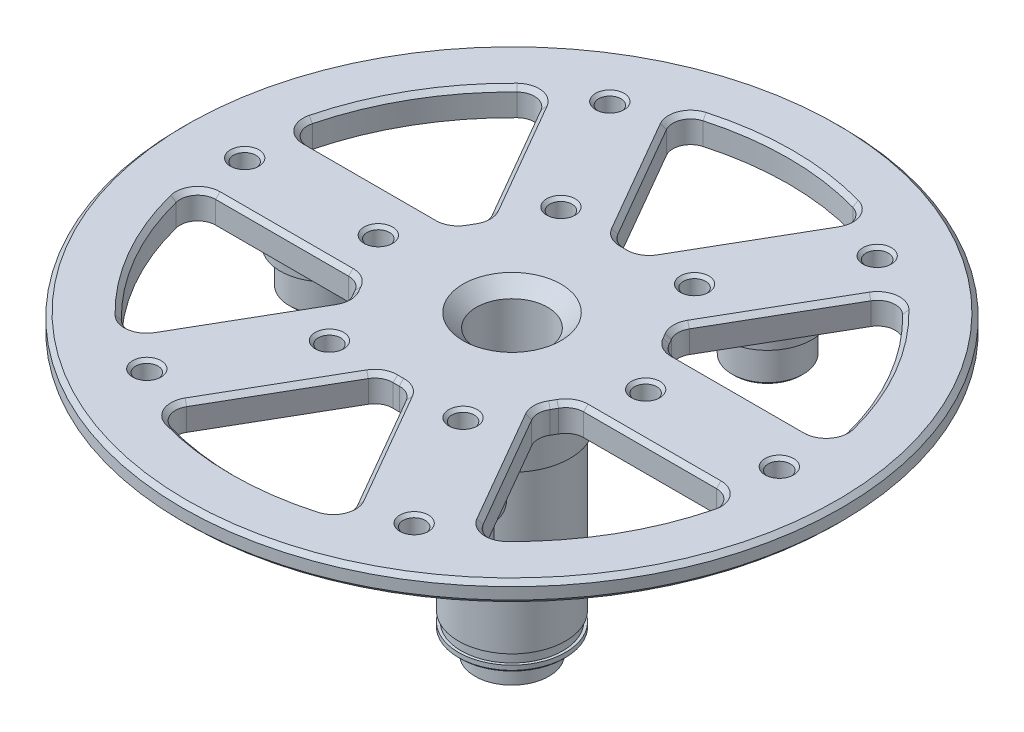
SolidWorks part; units mm, degrees
ref_plane "Front Plane" through (0, 0, 0) normal (0, 0, 1) x (1, 0, 0)
ref_plane "Top Plane" through (0, 0, 0) normal (0, 1, 0) x (1, 0, 0)
ref_plane "Right Plane" through (0, 0, 0) normal (1, 0, 0) x (0, 0, -1)
ref_axis "Axis1" through (0, 0, 0) along (0, 1, 0)
sketch "Sketch1" plane through (0, 0, 0) normal (0, 0, 1) x (1, 0, 0)
  line L0 (0, 0) -> (0, -6072.8457) construction
  line L2 (-3.15, -8.7) -> (-4, -8.7)
  line L3 (-4, -8.7) -> (-4, 19.6)
  line L4 (-4, 19.6) -> (-5.5, 21.1)
  line L5 (-5.5, 21.1) -> (-37, 21.1)
  line L6 (-32, 18.8) -> (-32, 18.1)
  line L7 (-32, 18.1) -> (-6.5, 18.1)
  line L8 (-6.5, 18.1) -> (-6.5, 10.15)
  line L9 (-6.5, 10.15) -> (-6, 10.15)
  line L10 (-6, 10.15) -> (-6, 5.15)
  line L13 (-33.5, 36.8027) -> (-33.5, 11.6549) construction
  line L14 (-9.5, 10.15) -> (9.5, 10.15) construction
  line L15 (6.5, -9.7) -> (-6.5, -9.7) construction
  line L18 (-6, -9.7) -> (-4.15, -9.7)
  line L20 (-32, 18.8) -> (-37, 18.8)
  line L21 (36.5, 17.8) -> (-36.5, 17.8) construction
  line L24 (-3.15, -12.2) -> (-3.15, -8.7)
  line L25 (-6, -8.95) -> (-6, -9.7)
  line L26 (8.5, 17.1) -> (-8.5, 17.1) construction
  line L27 (-4.15, -9.7) -> (-4.15, -12.2)
  line L28 (-4.15, -12.2) -> (-3.15, -12.2)
  line L29 (-6, -8.95) -> (-5.7, -8.95)
  line L31 (-6, -7.85) -> (-5.7, -7.85)
  line L32 (-5.7, -8.95) -> (-5.7, -7.85)
  line L33 (-37, 18.8) -> (-37, 21.1)
  line L34 (-33, 17.1) -> (-33, 17.8) construction
  line L35 (-37, 17.3) -> (-37, 6) construction
  line L36 (-10.5, 3.25) -> (-11, 3.25) construction
  line L37 (-6, 3.25) -> (-5.7, 3.25) construction
  line L39 (-6, 2.15) -> (-5.7, 2.15) construction
  line L40 (-5.7, 3.25) -> (-5.7, 2.15) construction
  line L41 (-6, 5.15) -> (-5.7, 5.15) construction
  line L43 (-6, 4.05) -> (-5.7, 4.05) construction
  line L44 (-5.7, 5.15) -> (-5.7, 4.05) construction
  line L45 (-6.25, 5.15) -> (6.25, 5.15) construction
  line L46 (-6, 4.05) -> (-6, 3.25) construction
  line L47 (-6, 2.15) -> (-6, -7.85)
  line L48 (-6, 2.15) -> (-6, 5.15)
  dimension "D1" = 8
  dimension "D2" = 3
  dimension "D3" = 1
  dimension "D4" = 12
  dimension "D5" = 135
  dimension "D6" = 1.5
  dimension "D7" = 1
  dimension "D8" = 8.3
  dimension "D9" = 13
  dimension "D10" = 0.3
  dimension "D11" = 1.1
  dimension "D12" = 0.75
  dimension "D13" = 2.5
  dimension "D14" = 1
  dimension "D15" = 33.5
  dimension "D16" = 1
  dimension "D17" = 1
revolve "Revolve1" add sketch "Sketch1" angle 360 about L0
chamfer "Chamfer1" distance 0.5 angle 45 1 edges at (0, -12.2, 3.15)
sketch "Sketch2" plane through (0, 0, 0) normal (0, 0, 1) x (1, 0, 0)
  line L0 (0, 0) -> (0, 50000) construction
  line L1 (-21, 33.1641) -> (-21, -6.3072) construction
  line L2 (-21, 18.1) -> (-26, 18.1)
  line L3 (-32, 18.1) -> (32, 18.1) construction
  line L4 (-32, 18.1) -> (-6.5, 18.1) construction
  line L5 (-26, 18.1) -> (-26, 17.1)
  line L6 (-26, 17.1) -> (-25, 17.1)
  line L7 (-25, 17.1) -> (-25, 13)
  line L8 (-25, 13) -> (-21, 13)
  line L9 (-21, 13) -> (-21, 18.1)
  dimension "D1" = 21
  dimension "D2" = 8
  dimension "D3" = 1
  dimension "D4" = 4.1
  dimension "D5" = 1
revolve "Planet bearing axis" add sketch "Sketch2" angle 360 about L1
chamfer "Chamfer2" distance 0.25 angle 45 1 edges at (-25, 13, 0)
pattern_circular "CirPattern1" count 3 over 360 about axis through (0, 0, 0) along (0, 1, 0) of "Planet bearing axis", "Chamfer2"
chamfer "Chamfer3" distance 0.25 angle 45 1 edges at (0, -9.7, 6)
chamfer "Chamfer4" distance 0.5 angle 45 3 edges at (0, 21.1, 37) (0, 18.8, 37) (0, 18.1, 6.5)
hole_wizard "M3x0.5 Tapped Hole1" positions "Sketch3" profile "Sketch4" tap size "M3x0.5" standard "ANSI Metric" end condition through all
sketch "Sketch3" plane through (0, 21.1, 0) normal (0, 1, 0) x (1, 0, 0)
  circle A2 centre (0, 0) radius 30 construction
  point P0 (-30, 0)
  dimension "D1" = 60
sketch "Sketch4" plane through (-30, 21.1, 0) normal (1, 0, 0) x (0, 0, 1)
  line L0 (0, 0) -> (0, 33.3)
  line L1 (0, 33.3) -> (1.25, 33.3)
  line L2 (1.25, 33.3) -> (1.25, 0.35)
  line L3 (1.25, 0.35) -> (1.6, 0)
  line L5 (1.6, 0) -> (0, 0)
  line L6 (-1.25, 0.35) -> (-1.6, 0) construction
  line L11 (0, -6.35) -> (0, 107.95) construction
  dimension "Thru Tap Drill Dia." = 2.5
  dimension "Thru Tap Drill Depth" = 33.3
  dimension "Near C'Sink Dia." = 3.2
  dimension "Near C'Sink Angle" = 90
cosmetic thread "Hole Thread1" parameters "D2"=3
hole_wizard "M3x0.5 Tapped Hole2" positions "Sketch5" profile "Sketch6" tap size "M3x0.5" standard "ANSI Metric" end condition through all
sketch "Sketch5" plane through (0, 21.1, 0) normal (0, 1, 0) x (1, 0, 0)
  circle A0 centre (0, 0) radius 15 construction
  point P0 (-15, 0)
  dimension "D1" = 30
sketch "Sketch6" plane through (-15, 21.1, 0) normal (1, 0, 0) x (0, 0, 1)
  line L0 (0, 0) -> (0, 33.3)
  line L1 (0, 33.3) -> (1.25, 33.3)
  line L2 (1.25, 33.3) -> (1.25, 0.35)
  line L3 (1.25, 0.35) -> (1.6, 0)
  line L5 (1.6, 0) -> (0, 0)
  line L6 (-1.25, 0.35) -> (-1.6, 0) construction
  line L11 (0, -6.35) -> (0, 107.95) construction
  dimension "Thru Tap Drill Dia." = 2.5
  dimension "Thru Tap Drill Depth" = 33.3
  dimension "Near C'Sink Dia." = 3.2
  dimension "Near C'Sink Angle" = 90
cosmetic thread "Hole Thread2" parameters "D2"=3
pattern_circular "CirPattern2" count 6 over 360 about axis through (0, 0, 0) along (0, 1, 0) of "M3x0.5 Tapped Hole1", "M3x0.5 Tapped Hole2"
sketch "Sketch7" plane through (0, 0, 0) normal (0, 1, 0) x (1, 0, 0)
  line L0 (0, 0) -> (-50000, 0) construction
  line L1 (0, 0) -> (-37.8615, -21.8593) construction
  line L2 (-19.7451, -23.8983) -> (-10.4286, -7.7617)
  line L3 (-11.9361, -5.1506) -> (-30.5691, -5.1506)
  arc A0 (-30.5691, -5.1506) -> (-19.7451, -23.8983) centre (0, 0) ccw
  arc A1 (-11.9361, -5.1506) -> (-10.4286, -7.7617) centre (0, 0) ccw
  point P11 (-26.8468, -15.5)
  point P12 (-11.2583, -6.5)
  dimension "D3" = 13
  dimension "D4" = 31
  dimension "D1" = 30
  dimension "D2" = 60
extrude "Cut-Extrude1" cut sketch "Sketch7" along normal through all
fillet "Fillet1" radius 2 4 edges at (-19.7451, 19.6, 23.8983) (-30.5691, 19.6, 5.1506) (-10.4286, 19.6, 7.7617) (-11.9361, 19.6, 5.1506)
chamfer "Chamfer5" distance 0.5 angle 45 8 edges at (-14.7832, 21.1, 15.304) (-10.7858, 21.1, 7.8173) (-19.9713, 21.1, 22.7452) (-11.2583, 21.1, 6.5) (-26.8468, 21.1, 15.5) (-12.1629, 21.1, 5.4321) (-29.6836, 21.1, 5.9231) (-20.6453, 21.1, 5.1506)
pattern_circular "CirPattern3" count 6 over 360 about axis through (0, 0, 0) along (0, 1, 0) of "Cut-Extrude1", "Fillet1", "Chamfer5"
